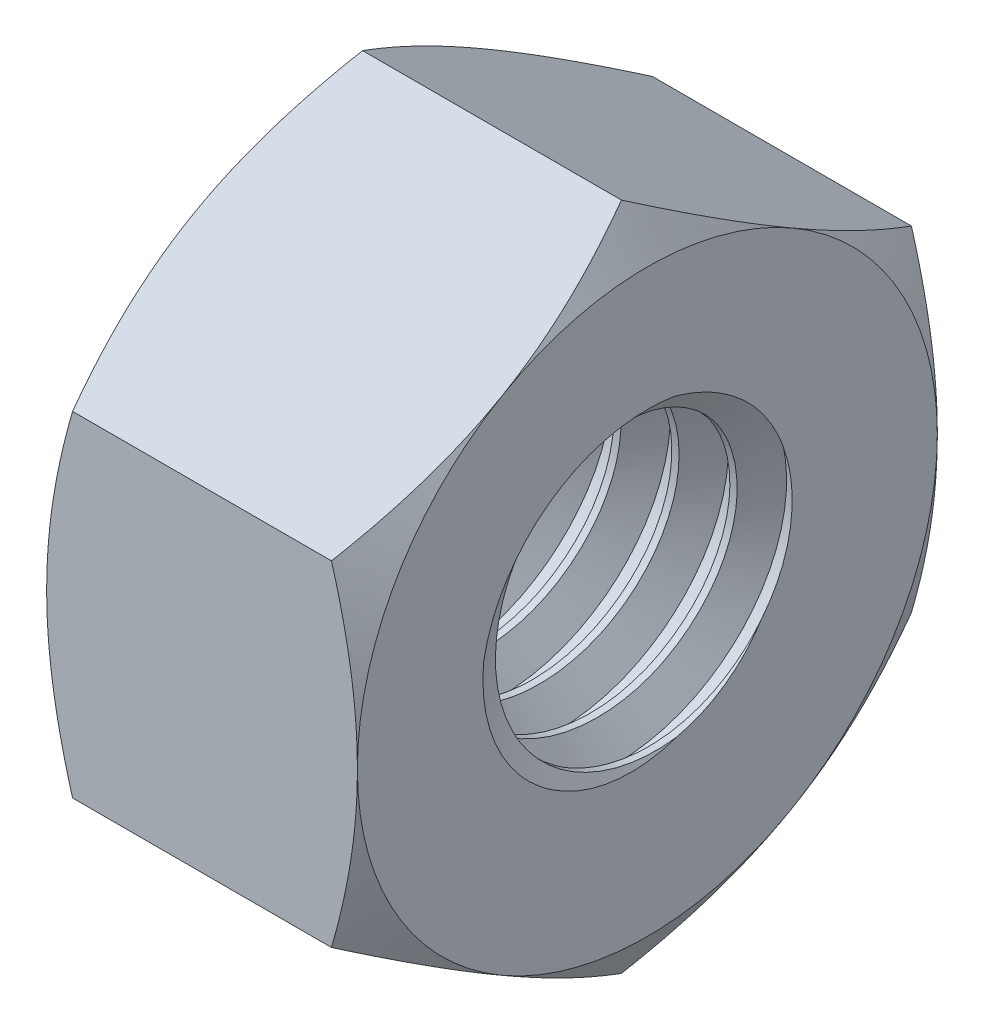
SolidWorks part; units mm, degrees
ref_plane "Front Plane" through (0, 0, 0) normal (0, 0, 1) x (1, 0, 0)
ref_plane "Top Plane" through (0, 0, 0) normal (0, 1, 0) x (1, 0, 0)
ref_plane "Right Plane" through (0, 0, 0) normal (1, 0, 0) x (0, 0, -1)
sketch "Sketch1" plane through (0, 0, 0) normal (0, 0, 1) x (1, 0, 0)
  line L0 (-1.875, 0) -> (1.875, 0) construction
  line L1 (-1.875, 3.5) -> (-1.5624, 4.0415)
  line L2 (-1.875, 1.63) -> (1.875, 1.63)
  line L3 (-1.875, 1.63) -> (-1.875, 4.0415)
  line L4 (-1.875, 4.0415) -> (1.875, 4.0415)
  line L5 (1.875, 1.63) -> (1.875, 4.0415)
  line L6 (-1.875, 4.0415) -> (-5.375, 2.0207) construction
  line L7 (-5.375, 2.0207) -> (-5.375, -2.0207) construction
  line L8 (-5.375, -2.0207) -> (-1.875, -4.0415) construction
  line L9 (-1.875, -4.0415) -> (1.625, -2.0207) construction
  line L10 (1.625, -2.0207) -> (1.625, 2.0207) construction
  line L11 (1.625, 2.0207) -> (-1.875, 4.0415) construction
  line L12 (0, -55) -> (0, 55) construction
  line L13 (1.875, 3.5) -> (1.5624, 4.0415)
  circle A0 centre (-1.875, 0) radius 3.5 construction
  point P4 (0, 0)
  dimension "D3" = 7
  dimension "D1" = 3.75
  dimension "D2" = 1.63
  dimension "D4" = 30
revolve "Revolve1" add sketch "Sketch1" angle 360 about L0 region at (0, 2.8162, 0)
sketch "Sketch2" plane through (1.875, 0, 0) normal (1, 0, 0) x (0, 0, -1)
  line L1 (0, 4.0415) -> (-3.5, 2.0207)
  line L2 (-3.5, 2.0207) -> (-3.5, -2.0207)
  line L3 (-3.5, -2.0207) -> (0, -4.0415)
  line L4 (0, -4.0415) -> (3.5, -2.0207)
  line L5 (3.5, -2.0207) -> (3.5, 2.0207)
  line L6 (3.5, 2.0207) -> (0, 4.0415)
  circle A0 centre (0, 0) radius 3.5 construction
  circle A1 centre (0, 0) radius 3.5 construction
extrude "Cut-Extrude1" cut sketch "Sketch2" against normal through all flip side to cut
thread "Thread1" pitch 0.7 method cut profile "Thread Profile1" start angle 0, offset 1, length 0, pitch 0.7, diameter 3.26
ref_plane "Plane1" through (-2.875, 0, -1.63) normal (0, 1, 0) x (0, 0, 1)
sketch "Thread Profile1" plane through (-2.875, 0, -1.63) normal (0, 1, 0) x (0, 0, 1)
  line L0 (0, 0) -> (0, 0.7) construction
  line L11 (0, 0) -> (0, 0.6125)
  line L12 (0, 0.6125) -> (-0.3789, 0.3937)
  line L13 (-0.3789, 0.3937) -> (-0.3789, 0.2187)
  line L15 (-0.3789, 0.2187) -> (0, 0)
  line L17 (-0.3789, 0.3062) -> (0, 0.3062) construction
  point P2 (0, 0)
  dimension "Pitch" = 0.7
  dimension "Profile_Angle" = 60
  dimension "Profile_Land" = 0.175
  dimension "Profile_Height" = 0.3789
